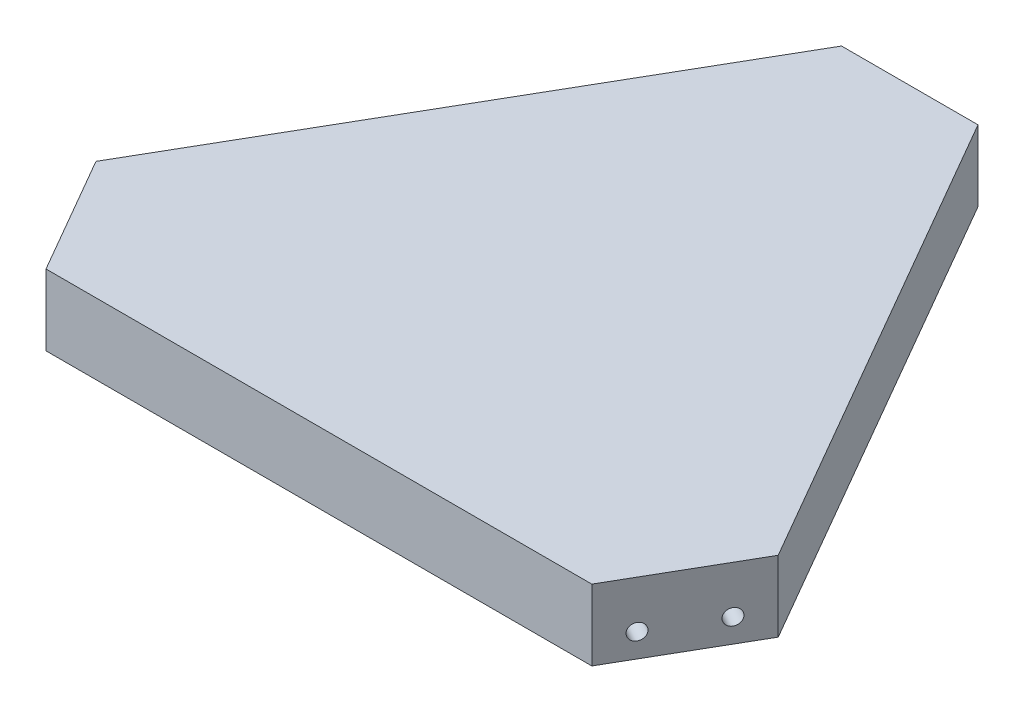
SolidWorks part; units mm, degrees
ref_plane "Front" through (0, 0, 0) normal (0, 0, 1) x (1, 0, 0)
ref_plane "Top" through (0, 0, 0) normal (0, 1, 0) x (1, 0, 0)
ref_plane "Right" through (0, 0, 0) normal (1, 0, 0) x (0, 0, -1)
sketch "Sketch1" plane through (0, 0, 0) normal (0, 1, 0) x (1, 0, 0)
  line L1 (-14.4338, 75) -> (-72.1688, -25)
  line L2 (-57.735, -50) -> (57.735, -50)
  line L3 (72.1688, -25) -> (14.4338, 75)
  line L4 (57.735, -50) -> (72.1688, -25)
  line L5 (14.4338, 75) -> (-14.4338, 75)
  line L6 (-72.1688, -25) -> (-57.735, -50)
  circle A2 centre (0, 0) radius 50 construction
  circle A3 centre (0, 0) radius 75 construction
  dimension "D1" = 100
  dimension "D2" = 150
extrude "Boss-Extrude1" add sketch "Sketch1" along normal blind 15
hole_wizard "M3 Clearance Hole1" positions "3DSketch1" profile "Sketch2" hole size "M3" standard "ANSI Metric"
sketch3d "3DSketch1"
  line L0 (57.735, 0, 50) -> (72.1688, 0, 25) construction
  line L1 (57.735, 15, 50) -> (57.735, 0, 50) construction
  line L2 (72.1688, 15, 25) -> (72.1688, 0, 25) construction
  point P0 (61.235, 5, 43.9378)
  point P2 (68.6688, 5, 31.0622)
  dimension "D1" = 5
  dimension "D2" = 7
  dimension "D3" = 5
  dimension "D4" = 7
sketch "Sketch2" plane through (61.235, 5, 43.9378) normal (0, 1, 0) x (0.5, 0, -0.866)
  line L0 (0, 0) -> (0, 25)
  line L1 (0, 25) -> (1.7, 23.9785)
  line L2 (1.7, 23.9785) -> (1.7, 0)
  line L5 (1.7, 0) -> (0, 0)
  line L10 (0, 25) -> (-1.7, 23.9785) construction
  line L11 (0, -6.35) -> (0, 107.95) construction
  dimension "Hole Dia." = 3.4
  dimension "Hole Depth" = 25
  dimension "Drill Angle" = 118
hole_wizard "M3 Clearance Hole2" positions "3DSketch2" profile "Sketch3" hole size "M3" standard "ANSI Metric"
sketch3d "3DSketch2"
  line L0 (14.4338, 15, -75) -> (14.4338, 0, -75) construction
  line L1 (14.4338, 0, -75) -> (-14.4338, 0, -75) construction
  line L2 (-14.4338, 15, -75) -> (-14.4338, 0, -75) construction
  point P0 (7.4338, 5, -75)
  point P2 (-7.4338, 5, -75)
  dimension "D1" = 7
  dimension "D2" = 5
  dimension "D3" = 5
  dimension "D4" = 7
sketch "Sketch3" plane through (7.4338, 5, -75) normal (1, 0, 0) x (0, 1, 0)
  line L0 (0, 0) -> (0, 25)
  line L1 (0, 25) -> (1.7, 23.9785)
  line L2 (1.7, 23.9785) -> (1.7, 0)
  line L5 (1.7, 0) -> (0, 0)
  line L10 (0, 25) -> (-1.7, 23.9785) construction
  line L11 (0, -6.35) -> (0, 107.95) construction
  dimension "Hole Dia." = 3.4
  dimension "Hole Depth" = 25
  dimension "Drill Angle" = 118
hole_wizard "M3 Clearance Hole3" positions "3DSketch3" profile "Sketch4" hole size "M3" standard "ANSI Metric"
sketch3d "3DSketch3"
  line L0 (-72.1688, 15, 25) -> (-72.1688, 0, 25) construction
  line L1 (-72.1688, 0, 25) -> (-57.735, 0, 50) construction
  line L2 (-57.735, 15, 50) -> (-57.735, 0, 50) construction
  point P0 (-68.6688, 5, 31.0622)
  point P2 (-61.235, 5, 43.9378)
  dimension "D1" = 7
  dimension "D2" = 5
  dimension "D3" = 5
  dimension "D4" = 7
sketch "Sketch4" plane through (-68.6688, 5, 31.0622) normal (0, 1, 0) x (0.5, 0, 0.866)
  line L0 (0, 0) -> (0, 25)
  line L1 (0, 25) -> (1.7, 23.9785)
  line L2 (1.7, 23.9785) -> (1.7, 0)
  line L5 (1.7, 0) -> (0, 0)
  line L10 (0, 25) -> (-1.7, 23.9785) construction
  line L11 (0, -6.35) -> (0, 107.95) construction
  dimension "Hole Dia." = 3.4
  dimension "Hole Depth" = 25
  dimension "Drill Angle" = 118
